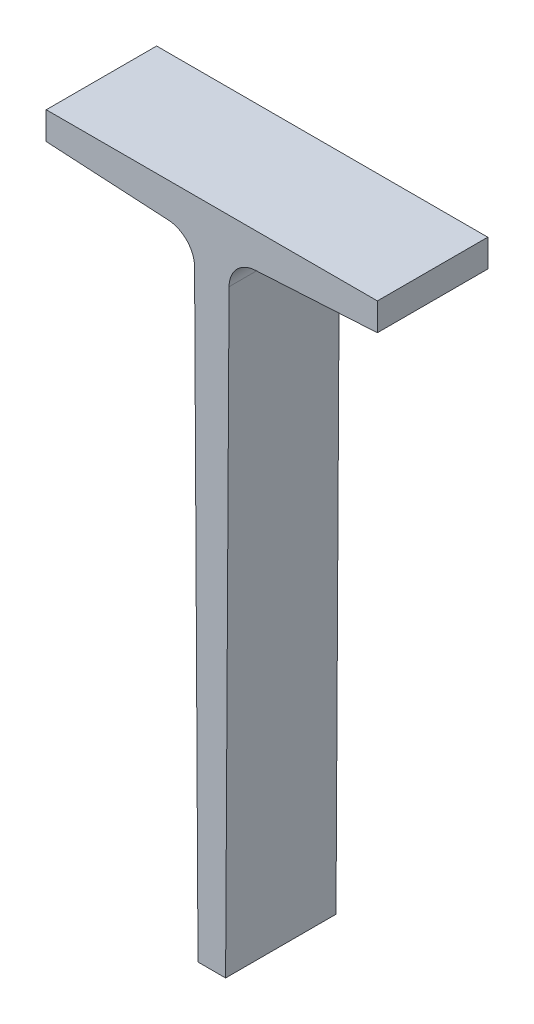
SolidWorks part; units mm, degrees
ref_plane "Plane1" through (0, 0, 0) normal (0, 0, 1) x (1, 0, 0)
ref_plane "Plane2" through (0, 0, 0) normal (0, 1, 0) x (-1, 0, 0)
ref_plane "Plane3" through (0, 0, 0) normal (1, 0, 0) x (0, 0, -1)
sketch "Sketch1" plane through (0, 0, 0) normal (0, 0, 1) x (1, 0, 0)
  line L0 (0, 0) -> (76.2, 0)
  line L1 (15.6984, 0) -> (-15.6984, 0) construction
  line L2 (34.925, -152.4) -> (34.1313, -14.2409)
  line L3 (28.139, -7.9375) -> (0, -6.35)
  line L4 (0, -9.8115) -> (0, 9.8115) construction
  line L5 (76.2, 0) -> (76.2, -6.35)
  line L6 (0, 0) -> (0, -6.35)
  line L7 (76.2, -6.35) -> (48.061, -7.9375)
  line L8 (42.0688, -14.2409) -> (41.275, -152.4)
  line L9 (34.925, -152.4) -> (41.275, -152.4)
  arc A1 (34.1313, -14.2409) -> (28.139, -7.9375) centre (27.7814, -14.2774) ccw
  arc A2 (48.061, -7.9375) -> (42.0688, -14.2409) centre (48.4186, -14.2774) ccw
  dimension "Radius_1" = 6.35
  dimension "H_Leg" = 76.2
  dimension "V_Leg" = 152.4
  dimension "t2" = 7.9375
extrude "Base-T" add sketch "Sketch1" along normal mid plane 25.4
